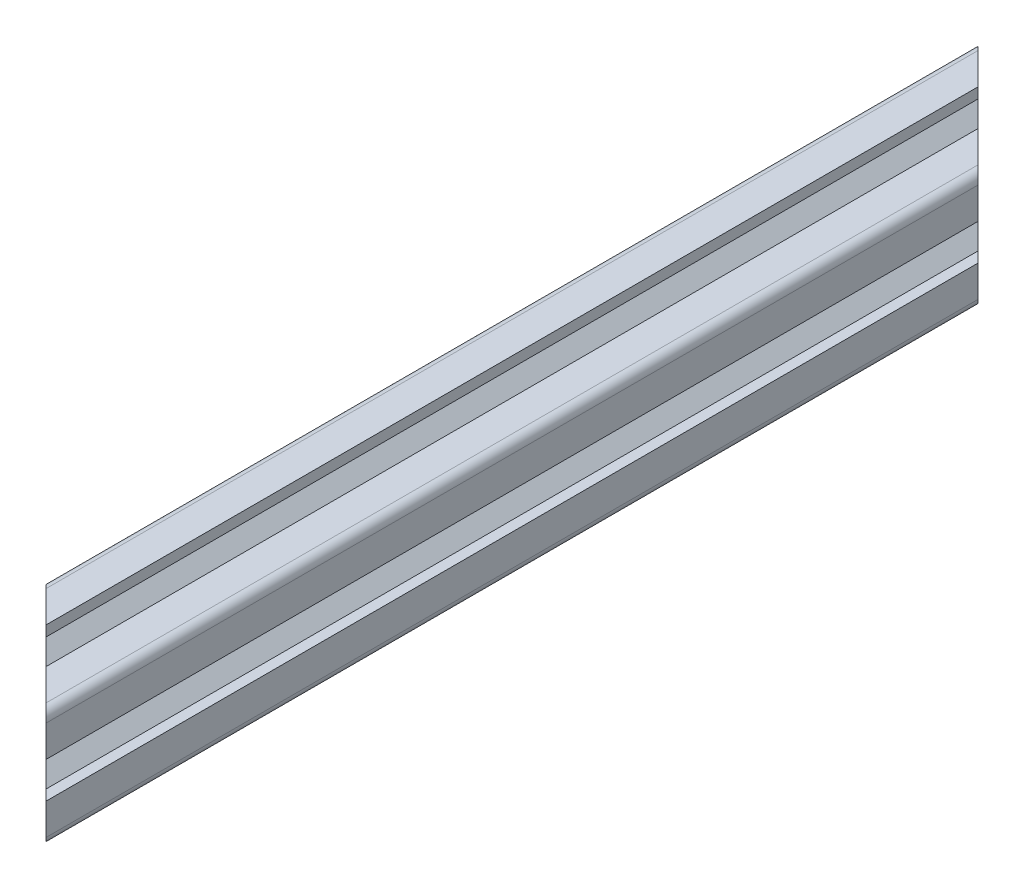
SolidWorks part; units mm, degrees
ref_plane "前视基准面" through (0, 0, 0) normal (0, 0, 1) x (1, 0, 0)
ref_plane "上视基准面" through (0, 0, 0) normal (0, 1, 0) x (1, 0, 0)
ref_plane "右视基准面" through (0, 0, 0) normal (1, 0, 0) x (0, 0, -1)
sketch "草图1" plane through (0, 0, 0) normal (0, 0, 1) x (1, 0, 0)
  line L0 (-10, -3.1) -> (-8.2, -3.1)
  line L1 (-8.5, 10) -> (8.5, 10)
  line L2 (-10, 8.5) -> (-10, -8.5)
  line L3 (-8.5, -10) -> (8.5, -10)
  line L4 (10, 8.5) -> (10, -8.5)
  line L5 (-10, 10) -> (10, -10) construction
  line L6 (-10, -10) -> (10, 10) construction
  line L7 (-3.0541, 3.1) -> (3.0541, 3.1)
  line L8 (-3.0541, 3.1) -> (-3.0541, -3.1)
  line L9 (-3.0541, -3.1) -> (3.0541, -3.1)
  line L10 (3.0541, 3.1) -> (3.0541, -3.1)
  line L11 (-3.0541, 3.1) -> (3.0541, -3.1) construction
  line L12 (-3.0541, -3.1) -> (3.0541, 3.1) construction
  line L13 (-8.2, -3.1) -> (-8.2, -5.5)
  line L14 (-8.2, -5.5) -> (-6.3971, -5.5)
  line L15 (-6.3971, -5.5) -> (-3.0541, -2.1571)
  line L16 (-5.5, 6.3971) -> (-2.1571, 3.0541)
  line L17 (-5.5, 8.2) -> (-5.5, 6.3971)
  line L18 (-3.1, 8.2) -> (-5.5, 8.2)
  line L19 (-3.1, 10) -> (-3.1, 8.2)
  line L20 (6.3971, 5.5) -> (3.0541, 2.1571)
  line L21 (8.2, 5.5) -> (6.3971, 5.5)
  line L22 (8.2, 3.1) -> (8.2, 5.5)
  line L23 (10, 3.1) -> (8.2, 3.1)
  line L24 (5.5, -6.3971) -> (2.1571, -3.0541)
  line L25 (5.5, -8.2) -> (5.5, -6.3971)
  line L26 (3.1, -8.2) -> (5.5, -8.2)
  line L27 (3.1, -10) -> (3.1, -8.2)
  line L28 (-3.1, -10) -> (-3.1, -8.2)
  line L29 (-3.1, -8.2) -> (-5.5, -8.2)
  line L30 (-5.5, -8.2) -> (-5.5, -6.3971)
  line L31 (-5.5, -6.3971) -> (-2.1571, -3.0541)
  line L32 (-8.2, 5.5) -> (-6.3971, 5.5)
  line L33 (-6.3971, 5.5) -> (-3.0541, 2.1571)
  line L34 (-8.2, 3.1) -> (-8.2, 5.5)
  line L35 (-10, 3.1) -> (-8.2, 3.1)
  line L36 (5.5, 8.2) -> (5.5, 6.3971)
  line L37 (5.5, 6.3971) -> (2.1571, 3.0541)
  line L38 (3.1, 8.2) -> (5.5, 8.2)
  line L39 (3.1, 10) -> (3.1, 8.2)
  line L40 (8.2, -5.5) -> (6.3971, -5.5)
  line L41 (6.3971, -5.5) -> (3.0541, -2.1571)
  line L42 (8.2, -3.1) -> (8.2, -5.5)
  line L43 (10, -3.1) -> (8.2, -3.1)
  circle A0 centre (0, 0) radius 2.5
  arc A1 (-10, 8.5) -> (-8.5, 10) centre (-8.5, 8.5) cw
  arc A2 (-10, -8.5) -> (-8.5, -10) centre (-8.5, -8.5) ccw
  arc A3 (8.5, 10) -> (10, 8.5) centre (8.5, 8.5) cw
  arc A4 (10, -8.5) -> (8.5, -10) centre (8.5, -8.5) cw
  point P0 (0, 0)
  point P20 (0, 0)
  point P26 (0, 0)
  point P32 (0, 0)
  point P38 (0, 0)
  point P60 (0, 0)
  dimension "D1" = 4
  dimension "D3" = 1.5
  dimension "D4" = 1.5
  dimension "D5" = 1.5
  dimension "D2" = 4
extrude "凸台-拉伸1" add sketch "草图1" along normal blind 180 contours A1 L2 L35 L34 L32 L33 L8 L7 L16 L17 L18 L19 L1 | A3 L1 L39 L38 L36 L37 L7 L10 L20 L21 L22 L23 L4 | L10 L7 L8 L9 A0 | A4 L4 L43 L42 L40 L41 L10 L9 L24 L25 L26 L27 L3 | L2 A2 L3 L28 L29 L30 L31 L9 L8 L15 L14 L13 L0 region at (-6.9209, -6.9203, 0) region at (-6.9209, 6.9203, 0) region at (-2.9671, 0, 0) region at (6.9209, -6.9203, 0) region at (6.9209, 6.9203, 0)
sketch "草图2" plane through (0, 10, 0) normal (0, 1, 0) x (1, 0, 0)
  line L0 (-10, 0) -> (10, 0)
  line L1 (10, 0) -> (10, -20)
  line L2 (10, -180) -> (10, 0) construction
  line L3 (10, -20) -> (-10, 0)
  line L4 (-10, -180) -> (-10, -160)
  line L5 (-10, -180) -> (-10, 0) construction
  line L6 (-10, -160) -> (10, -180)
  line L7 (10, -180) -> (-10, -180)
extrude "切除-拉伸1" cut sketch "草图2" against normal through all
